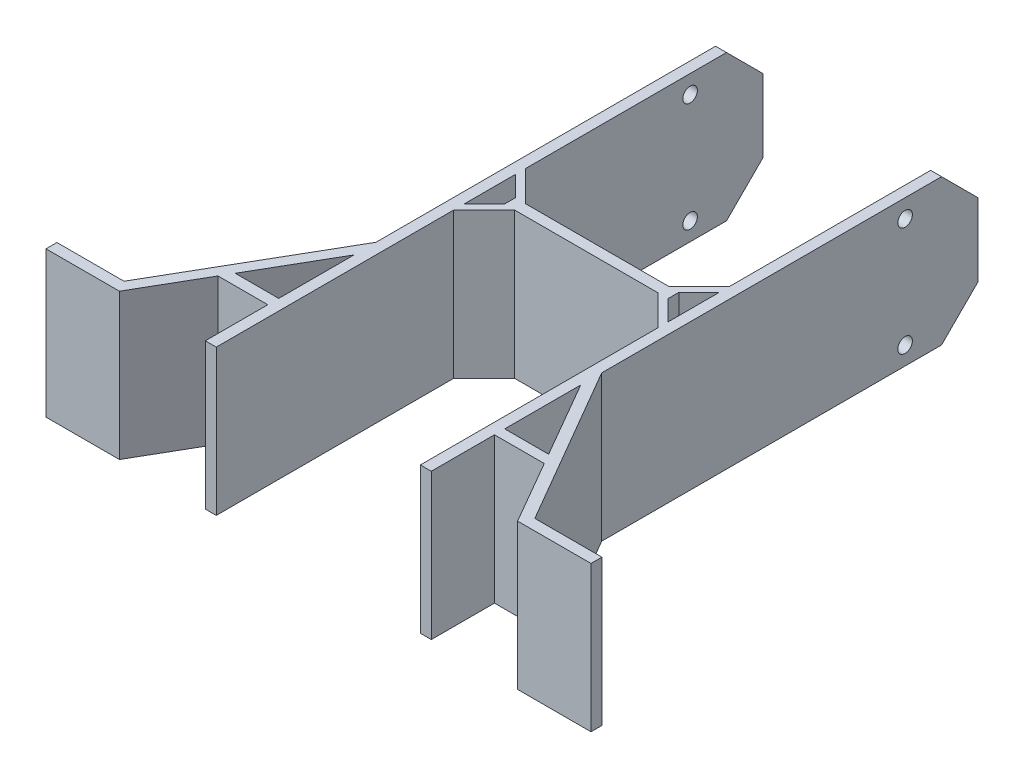
SolidWorks part; units mm, degrees
ref_plane "Alzado" through (0, 0, 0) normal (0, 0, 1) x (1, 0, 0)
ref_plane "Planta" through (0, 0, 0) normal (0, 1, 0) x (1, 0, 0)
ref_plane "Vista lateral" through (0, 0, 0) normal (1, 0, 0) x (0, 0, -1)
sketch "Croquis1" plane through (0, 0, 0) normal (0, 1, 0) x (1, 0, 0)
  line L0 (-32.5, 0) -> (32.5, 0) construction
  line L1 (-28, 9.8655) -> (-19.6345, 1.5)
  line L2 (-28, -75) -> (-31, -75)
  line L3 (-28, -75) -> (-28, -9.8655)
  line L4 (-28, 75) -> (-31, 75)
  line L5 (-31, -75) -> (-31, -57.8568)
  line L6 (-28, -75) -> (-31, 75) construction
  line L7 (-28, 75) -> (-31, -75) construction
  line L8 (31, -75) -> (28, -75)
  line L9 (31, -75) -> (31, -57.6674)
  line L10 (31, 75) -> (28, 75)
  line L11 (28, -75) -> (28, -9.8655)
  line L12 (31, -75) -> (28, 75) construction
  line L13 (31, 75) -> (28, -75) construction
  line L14 (-19.6345, 1.5) -> (19.6345, 1.5)
  line L15 (19.6345, 1.5) -> (28, 9.8655)
  line L16 (-28, -9.8655) -> (-19.6345, -1.5)
  line L17 (-19.6345, -1.5) -> (19.6345, -1.5)
  line L18 (19.6345, -1.5) -> (28, -9.8655)
  line L19 (0, 1.5) -> (0, -1.5) construction
  line L20 (-28, -7.037) -> (-22.455, -1.492)
  line L21 (-22.455, -1.492) -> (-22.455, 1.492)
  line L22 (-22.455, 1.492) -> (-28, 7.037)
  line L23 (28, -7.0117) -> (22.455, -1.4667)
  line L24 (22.455, -1.4667) -> (22.455, 1.4667)
  line L25 (22.455, 1.4667) -> (28, 7.0117)
  line L26 (-28, 9.8655) -> (-28, 75)
  line L27 (-28, -7.037) -> (-28, 7.037)
  line L28 (28, -7.0117) -> (28, 7.0117)
  line L29 (28, 9.8655) -> (28, 75)
  line L30 (31, -33.9913) -> (43.0467, -54.8568)
  line L31 (54.6764, -75) -> (74.8206, -75)
  line L32 (74.8206, -75) -> (74.8206, -72)
  line L33 (74.8206, -72) -> (56.4084, -72)
  line L34 (56.4084, -72) -> (31, -28.244)
  line L35 (-31, -34.1807) -> (-42.9373, -54.8568)
  line L36 (-54.567, -75) -> (-74.7113, -75)
  line L37 (-74.7113, -75) -> (-74.7113, -72)
  line L38 (-74.7113, -72) -> (-56.2991, -72)
  line L39 (-56.2991, -72) -> (-31, -28.1807)
  line L40 (-44.6694, -57.8568) -> (-31, -57.8568)
  line L41 (-42.9373, -54.8568) -> (-31, -54.8568)
  line L42 (44.6694, -57.6674) -> (31, -57.6674)
  line L43 (43.0467, -54.8568) -> (31, -54.8568)
  line L44 (-44.6694, -57.8568) -> (-54.567, -75)
  line L45 (-31, -54.8568) -> (-31, -34.1807)
  line L46 (-31, -28.1807) -> (-31, 75)
  line L47 (44.6694, -57.6674) -> (54.6764, -75)
  line L48 (31, -54.8568) -> (31, -33.9913)
  line L49 (31, -28.244) -> (31, 75)
  point P3 (29.5, 0)
  point P4 (0, 0)
  point P7 (-29.5, 0)
  point P20 (0, 0)
  point P23 (0, 1.5)
  point P24 (0, -1.5)
  point P34 (22.455, 0)
  point P56 (0, 0)
  point P57 (-56.2132, -68.1253)
  point P58 (-56.2491, -75)
  point P59 (-31, -31.2644)
  point P60 (0, 0)
  point P61 (-31, -31.2644)
  point P62 (-31, -31.2644)
  point P63 (-31, -31.2644)
  point P64 (-54.9544, -75)
  point P66 (-31, -34.1807)
  point P67 (0, 0)
  dimension "D1" = 3
  dimension "D2" = 56
  dimension "D3" = 3
  dimension "D4" = 2
  dimension "D5" = 2
  dimension "D6" = 150
  dimension "D7" = 60
  dimension "D8" = 60
  dimension "D9" = 3
  dimension "D10" = 3
  dimension "D11" = 3
extrude "Saliente-Extruir1" add sketch "Croquis1" along normal blind 40
sketch "Croquis2" plane through (31, 0, 0) normal (1, 0, 0) x (0, 0, -1)
  line L0 (75, 40) -> (75, 0) construction
  line L1 (55, 35) -> (55, 5) construction
  line L2 (-75, 40) -> (-57.6674, 40) construction
  circle A0 centre (55, 35) radius 2
  circle A1 centre (55, 5) radius 2
  point P4 (55, 20)
  dimension "D1" = 4
  dimension "D2" = 20
  dimension "D3" = 20
  dimension "D4" = 30
extrude "Cortar-Extruir1" cut sketch "Croquis2" against normal through all
chamfer "Chaflán1" distance 10 angle 45 4 edges at (-29.5, 40, -75) (-29.5, 0, -75) (29.5, 0, -75) (29.5, 40, -75)
